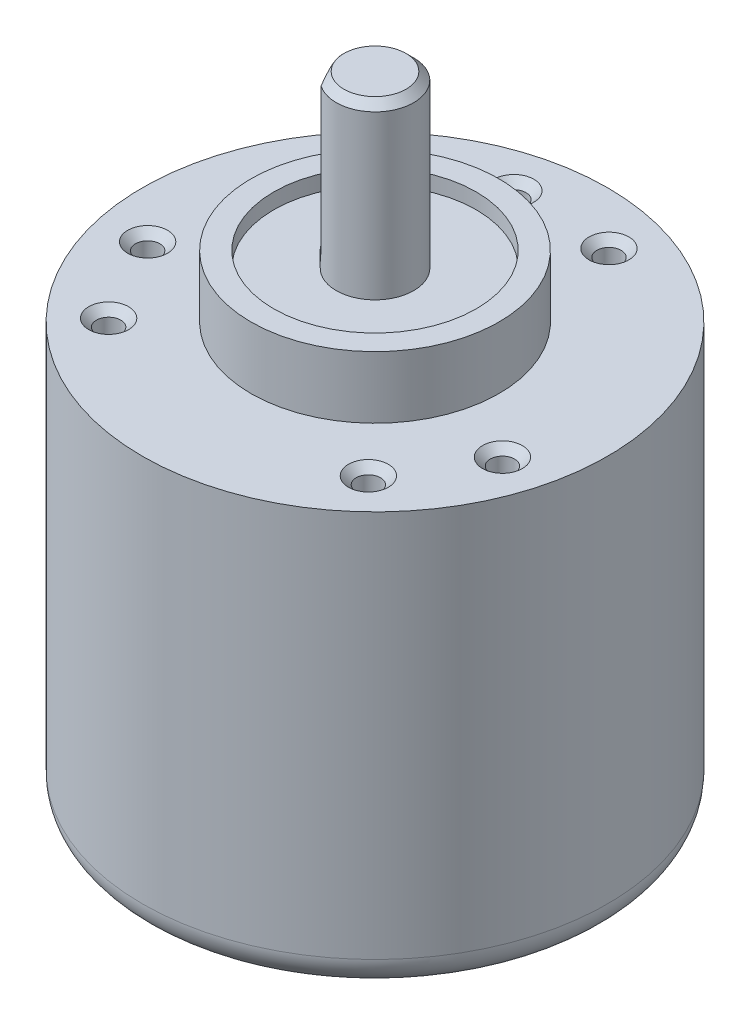
SolidWorks part; units mm, degrees
ref_plane "Front Plane" through (0, 0, 0) normal (0, 0, 1) x (1, 0, 0)
ref_plane "Top Plane" through (0, 0, 0) normal (0, 1, 0) x (1, 0, 0)
ref_plane "Right Plane" through (0, 0, 0) normal (1, 0, 0) x (0, 0, -1)
sketch "Sketch1" plane through (0, 0, 0) normal (0, 1, 0) x (1, 0, 0)
  circle A0 centre (0, 0) radius 19.05
  dimension "D1" = 38.1
extrude "Boss-Extrude1" add sketch "Sketch1" along normal blind 34.29
sketch "Sketch3" plane through (0, 34.29, 0) normal (0, 1, 0) x (1, 0, 0)
  circle A0 centre (0, 0) radius 10.16
  dimension "D1" = 20.32
extrude "Boss-Extrude3" add sketch "Sketch3" along normal blind 5.08
sketch "Sketch4" plane through (0, 39.37, 0) normal (0, 1, 0) x (1, 0, 0)
  line L0 (-3.0146, 0.9964) -> (-1.8006, -2.615)
  arc A0 (-1.8006, -2.615) -> (-3.0146, 0.9964) centre (0, 0) ccw
  dimension "D1" = 6.35
  dimension "D2" = 3.81
extrude "Boss-Extrude4" add sketch "Sketch4" along normal blind 12.7
fillet "Fillet1" radius 2.54 1 edges at (0, 0, 19.05)
chamfer "Chamfer1" distance 0.635 angle 45 1 edges at (3.0095, 52.07, -1.0116)
sketch "Sketch5" plane through (0, 34.29, 0) normal (0, 1, 0) x (1, 0, 0)
  circle A0 centre (0, 0) radius 15.4305 construction
  circle A1 centre (-11.1788, -10.6365) radius 0.997
  circle A2 centre (-14.9994, -3.622) radius 0.997
  circle A3 centre (-14.8009, 4.3629) radius 0.9969 [skipped]
  circle A4 centre (-10.6365, 11.1788) radius 0.9969 [skipped]
  circle A5 centre (-3.622, 14.9994) radius 0.9969
  circle A6 centre (4.3629, 14.8009) radius 0.997
  circle A7 centre (11.1788, 10.6365) radius 0.9969 [skipped]
  circle A8 centre (14.9994, 3.622) radius 0.997 [skipped]
  circle A9 centre (14.8009, -4.3629) radius 0.997
  circle A10 centre (10.6365, -11.1788) radius 0.997
  circle A11 centre (3.622, -14.9994) radius 0.9969 [skipped]
  circle A12 centre (-4.3629, -14.8009) radius 0.997 [skipped]
  dimension "D1" = 30.861
  dimension "D2" = 1.9939
  dimension "D3" = 12
extrude "Cut-Extrude1" cut sketch "Sketch5" against normal blind 12.7
chamfer "Chamfer2" distance 0.635 angle 45 6 edges at (10.6365, 34.29, 12.1758) (14.8009, 34.29, 5.3599) (4.3629, 34.29, -13.8039) (-3.622, 34.29, -14.0024) (-14.9994, 34.29, 4.619) (-11.1788, 34.29, 11.6334)
sketch "Sketch6" plane through (0, 39.37, 0) normal (0, 1, 0) x (1, 0, 0)
  circle A0 centre (0, 0) radius 8.2967
  circle A1 centre (0, 0) radius 3.175
extrude "Cut-Extrude2" cut sketch "Sketch6" against normal blind 1.27
